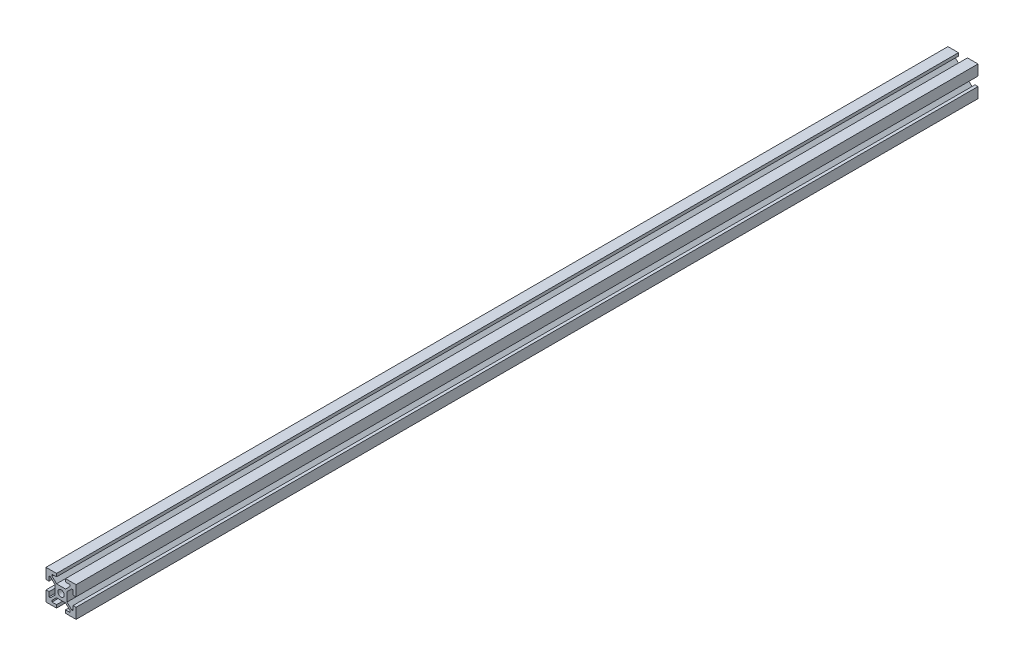
SolidWorks part; units mm, degrees
ref_plane "正面" through (0, 0, 0) normal (0, 0, 1) x (1, 0, 0)
ref_plane "平面" through (0, 0, 0) normal (0, 1, 0) x (1, 0, 0)
ref_plane "右側面" through (0, 0, 0) normal (1, 0, 0) x (0, 0, -1)
sketch "ｽｹｯﾁ2" plane through (0, 0, 0) normal (0, 0, 1) x (1, 0, 0)
  line L0 (0, 0) -> (0, 10) construction
  line L1 (-10, -10) -> (10, -10) construction
  line L2 (-10, -10) -> (-10, 10) construction
  line L3 (-10, 10) -> (10, 10) construction
  line L4 (10, -10) -> (10, 10) construction
  line L5 (-10, -10) -> (10, 10) construction
  line L6 (-10, 10) -> (10, -10) construction
  line L8 (3, 4) -> (-3, 4)
  line L9 (-6, 7) -> (6, 7) construction
  line L10 (-6, 8) -> (-6, 7)
  line L11 (6, 8) -> (6, 7)
  line L12 (-6, 7) -> (-3, 4)
  line L13 (3, 4) -> (6, 7)
  line L14 (-6, 8) -> (-3, 8)
  line L15 (-3, 8) -> (-3, 10)
  line L16 (-3, 10) -> (-10, 10)
  line L17 (6, 8) -> (3, 8)
  line L18 (3, 8) -> (3, 10)
  line L19 (3, 10) -> (10, 10)
  line L20 (7, 6) -> (4, 3)
  line L21 (4, -3) -> (4, 3)
  line L22 (4, -3) -> (7, -6)
  line L23 (8, -6) -> (8, -3)
  line L24 (8, -6) -> (7, -6)
  line L25 (8, -3) -> (10, -3)
  line L26 (10, -3) -> (10, -10)
  line L27 (8, 3) -> (10, 3)
  line L28 (10, 3) -> (10, 10)
  line L29 (8, 6) -> (8, 3)
  line L30 (8, 6) -> (7, 6)
  line L31 (6, -7) -> (3, -4)
  line L32 (-3, -4) -> (3, -4)
  line L33 (-3, -4) -> (-6, -7)
  line L34 (-6, -8) -> (-3, -8)
  line L35 (-6, -8) -> (-6, -7)
  line L36 (-3, -8) -> (-3, -10)
  line L37 (-3, -10) -> (-10, -10)
  line L38 (3, -8) -> (3, -10)
  line L39 (3, -10) -> (10, -10)
  line L40 (6, -8) -> (3, -8)
  line L41 (6, -8) -> (6, -7)
  line L42 (-7, -6) -> (-4, -3)
  line L43 (-4, 3) -> (-4, -3)
  line L44 (-4, 3) -> (-7, 6)
  line L45 (-8, 6) -> (-8, 3)
  line L46 (-8, 6) -> (-7, 6)
  line L47 (-8, 3) -> (-10, 3)
  line L48 (-10, 3) -> (-10, 10)
  line L49 (-8, -3) -> (-10, -3)
  line L50 (-10, -3) -> (-10, -10)
  line L51 (-8, -6) -> (-8, -3)
  line L52 (-8, -6) -> (-7, -6)
  circle A0 centre (0, 0) radius 2.1
  point P0 (0, 0)
  point P11 (0, 10)
  point P14 (0, 4)
  point P17 (0, 7)
  dimension "D8" = 4.2
  dimension "D1" = 20
  dimension "D2" = 6
  dimension "D3" = 2
  dimension "D4" = 4
  dimension "D5" = 12
  dimension "D6" = 6
  dimension "D7" = 4
extrude "ﾎﾞｽ - 押し出し1" add sketch "ｽｹｯﾁ2" along normal blind 600
